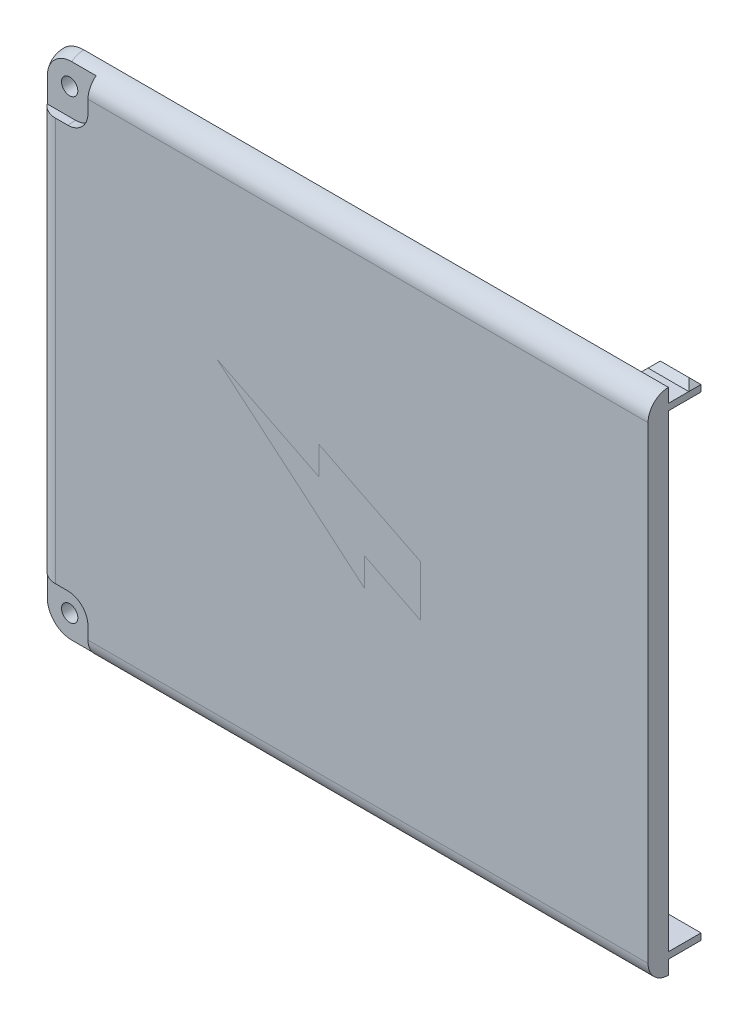
SolidWorks part; units mm, degrees
ref_plane "Front" through (0, 0, 0) normal (0, 0, 1) x (1, 0, 0)
ref_plane "Top" through (0, 0, 0) normal (0, 1, 0) x (1, 0, 0)
ref_plane "Right" through (0, 0, 0) normal (1, 0, 0) x (0, 0, -1)
sketch "Sketch1" plane through (0, 0, 0) normal (0, 0, 1) x (1, 0, 0)
  line L7 (145.5, 120) -> (145.5, -5)
  line L9 (145.5, -5) -> (2, -5)
  line L10 (-5, 2) -> (-5, 113)
  line L11 (2, 120) -> (145.5, 120)
  line L12 (145.5, -5) -> (2, -5)
  line L13 (-5, 2) -> (-5, 113)
  line L14 (2, 120) -> (145.5, 120)
  arc A6 (-5, 2) -> (2, -5) centre (2, 2) ccw
  arc A7 (2, 120) -> (-5, 113) centre (2, 113) ccw
  arc A8 (-5, 2) -> (2, -5) centre (2, 2) ccw
  arc A9 (2, 120) -> (-5, 113) centre (2, 113) ccw
  dimension "D1" = 0
extrude "Boss-Extrude1" add sketch "Sketch1" along normal blind 5
fillet "Fillet1" radius 5 5 edges at (73.75, -5, 5) (-2.9497, -2.9497, 5) (-5, 57.5, 5) (-2.9497, 117.9497, 5) (73.75, 120, 5)
ref_plane "Plane1" through (0, 115, 0) normal (0, 1, 0) x (1, 0, 0)
ref_plane "Plane2" through (0, 57.5, 0) normal (0, 1, 0) x (1, 0, 0)
sketch "Sketch2" plane through (0, 0, 5) normal (0, 0, 1) x (1, 0, 0)
  circle A0 centre (1.5, 113.5) radius 2
  circle A1 centre (1.5, 1.5) radius 2
  dimension "D1" = 4
extrude "Cut-Extrude1" cut sketch "Sketch2" against normal through all
sketch "Sketch3" plane through (0, 0, 0) normal (0, 0, -1) x (-1, 0, 0)
  line L5 (-18, 115) -> (0, 97)
  line L6 (-18, 0) -> (0, 18)
  line L9 (-140.5, 0) -> (-2, 0)
  line L10 (0, 2) -> (0, 113)
  line L11 (-2, 115) -> (-140.5, 115)
  line L12 (-140.5, 115) -> (-140.5, 0)
  line L13 (-140.5, 0) -> (-2, 0)
  line L14 (0, 2) -> (0, 113)
  line L15 (-2, 115) -> (-140.5, 115)
  line L16 (-140.5, 115) -> (-140.5, 0)
  arc A4 (-2, 0) -> (0, 2) centre (-2, 2) ccw
  arc A5 (0, 113) -> (-2, 115) centre (-2, 113) ccw
  arc A6 (-2, 0) -> (0, 2) centre (-2, 2) ccw
  arc A7 (0, 113) -> (-2, 115) centre (-2, 113) ccw
  dimension "D2" = 18
  dimension "D3" = 18
  dimension "D1" = 5
extrude "Cut-Extrude2" cut sketch "Sketch3" against normal blind 2 contours L15 L16 L13 L6 L14 L5 region at (71.5647, 57.5, 0)
sketch "Sketch4" plane through (0, 0, 5) normal (0, 0, 1) x (1, 0, 0)
  line L0 (145.5, 120) -> (2, 120) construction
  line L1 (-5, 107) -> (3, 107)
  line L2 (-5, 107) -> (-5, 120)
  line L3 (-5, 120) -> (8, 120)
  line L4 (8, 112) -> (8, 120)
  line L5 (-5, 113) -> (-5, 2) construction
  arc A0 (3, 107) -> (8, 112) centre (3, 112) ccw
  point P4 (1.5, 120)
  point P9 (1.5, 113.5)
  dimension "D1" = 5
extrude "Cut-Extrude3" cut sketch "Sketch4" against normal blind 2
mirror "Mirror1" about plane through (0, 57.5, 0) normal (0, 1, 0) of "Cut-Extrude3"
sketch "Sketch5" plane through (0, 0, 5) normal (0, 0, 1) x (1, 0, 0)
  circle A0 centre (1.5, 113.5) radius 4
  circle A1 centre (1.5, 1.5) radius 4
  dimension "D1" = 8
extrude "Cut-Extrude4" [suppressed] cut sketch "Sketch5" against normal blind 2
sketch "Sketch6" plane through (0, 0, 5) normal (0, 0, 1) x (1, 0, 0)
  line L0 (-5, 113) -> (-5, 2) construction
  line L1 (-5, -5) -> (145.5, -5) construction
  line L2 (-5, -5) -> (-5, 120) construction
  line L3 (-5, 120) -> (145.5, 120) construction
  line L4 (145.5, -5) -> (145.5, 120) construction
  line L5 (-5, -5) -> (145.5, 120) construction
  line L6 (-5, 120) -> (145.5, -5) construction
  line L7 (2, -5) -> (145.5, -5) construction
  line L8 (89.6598, 57.5) -> (89.6598, 45)
  line L9 (89.6598, 45) -> (75.8402, 51.9098)
  line L10 (75.8402, 51.9098) -> (75.8402, 45)
  line L11 (75.8402, 45) -> (39.6598, 75.5902)
  line L13 (64.6598, 57.5) -> (64.6598, 70) construction
  line L14 (64.6598, 70) -> (89.6598, 57.5)
  line L15 (64.6598, 70) -> (89.6598, 70) construction
  line L16 (89.6598, 70) -> (89.6598, 45) construction
  line L17 (64.6598, 57.5) -> (75.8402, 51.9098) construction
  line L18 (64.6598, 70) -> (64.6598, 63.0902)
  line L19 (64.6598, 63.0902) -> (39.6598, 75.5902)
  line L20 (64.6598, 57.5) -> (70.25, 57.5) construction
  line L21 (70.25, 57.5) -> (70.25, 54.7049) construction
  line L22 (64.6598, 70) -> (64.6598, 75.5902) construction
  line L23 (64.6598, 75.5902) -> (39.6598, 75.5902) construction
  point P0 (70.25, 57.5)
  point P22 (70.25, 54.7049)
  dimension "D1" = 50
extrude "Cut-Extrude5" cut sketch "Sketch6" against normal blind 1
sketch "Sketch7" plane through (0, 0, 4) normal (0, 0, 1) x (1, 0, 0)
  line L7 (89.6598, 57.5) -> (64.6598, 70)
  line L8 (64.6598, 70) -> (64.6598, 63.0902)
  line L9 (64.6598, 63.0902) -> (39.6598, 75.5902)
  line L10 (39.6598, 75.5902) -> (75.8402, 45)
  line L11 (75.8402, 45) -> (75.8402, 51.9098)
  line L12 (75.8402, 51.9098) -> (89.6598, 45)
  line L13 (89.6598, 45) -> (89.6598, 57.5)
  line L14 (89.6598, 57.5) -> (64.6598, 70)
  line L15 (64.6598, 70) -> (64.6598, 63.0902)
  line L16 (64.6598, 63.0902) -> (39.6598, 75.5902)
  line L17 (39.6598, 75.5902) -> (75.8402, 45)
  line L18 (75.8402, 45) -> (75.8402, 51.9098)
  line L19 (75.8402, 51.9098) -> (89.6598, 45)
  line L20 (89.6598, 45) -> (89.6598, 57.5)
  dimension "D1" = 0
extrude "Boss-Extrude2" add sketch "Sketch7" along normal up to surface (1 mm away) separate body up to face at (71.4256, 58.2986, 5)
sketch "Sketch8" plane through (0, 0, 0) normal (0, 0, -1) x (-1, 0, 0)
  line L0 (-145.5, -5) -> (-145.5, 120) construction
  line L1 (-145.5, 116.6) -> (-135.5, 116.6)
  line L2 (-145.5, 116.6) -> (-145.5, 115)
  line L3 (-145.5, 115) -> (-135.5, 115)
  line L4 (-135.5, 116.6) -> (-135.5, 115)
  line L5 (-18, 115) -> (-140.5, 115) construction
  dimension "D1" = 1.6
  dimension "D2" = 10
extrude "Boss-Extrude3" add sketch "Sketch8" along normal blind 8
sketch "Sketch9" plane through (0, 116.6, 0) normal (0, 1, 0) x (1, 0, 0)
  line L0 (145.5, 8) -> (145.5, 0) construction
  line L1 (135.5, 8) -> (145.5, 8)
  line L2 (135.5, 8) -> (135.5, 5)
  line L3 (135.5, 5) -> (145.5, 5)
  line L4 (145.5, 8) -> (145.5, 5)
  dimension "D1" = 3
extrude "Boss-Extrude4" add sketch "Sketch9" along normal blind 1.5 draft 45
mirror "Mirror2" about plane through (0, 57.5, 0) normal (0, 1, 0) of "Boss-Extrude4", "Boss-Extrude3"
